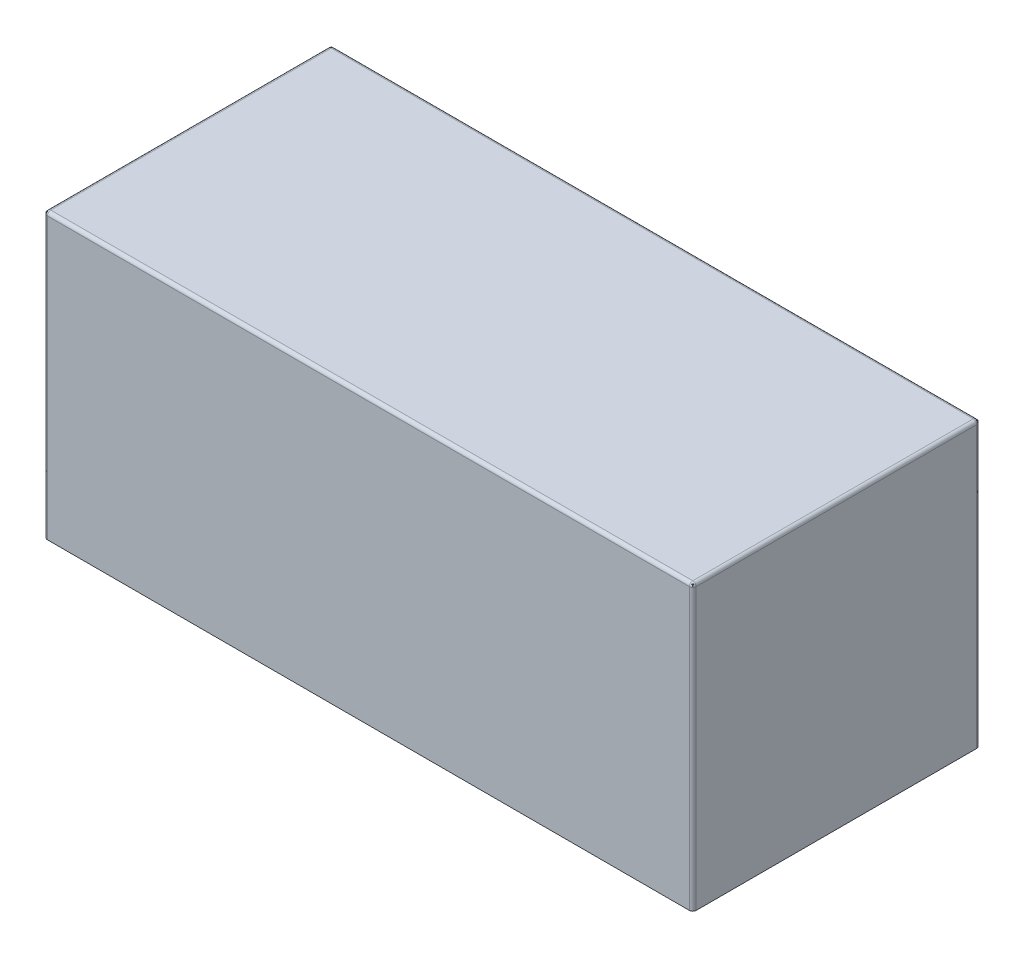
SolidWorks part; units mm, degrees
material "Alumina"
ref_plane "Front Plane" through (0, 0, 0) normal (0, 0, 1) x (1, 0, 0)
ref_plane "Top Plane" through (0, 0, 0) normal (0, 1, 0) x (1, 0, 0)
ref_plane "Right Plane" through (0, 0, 0) normal (1, 0, 0) x (0, 0, -1)
sketch "Sketch2" plane through (0, 0, 0) normal (0, 1, 0) x (1, 0, 0)
  line L1 (-480, 212.5) -> (480, 212.5)
  line L2 (-480, 212.5) -> (-480, -212.5)
  line L3 (-480, -212.5) -> (480, -212.5)
  line L4 (480, 212.5) -> (480, -212.5)
  line L5 (-480, 212.5) -> (480, -212.5) construction
  line L6 (-480, -212.5) -> (480, 212.5) construction
  line L7 (-478.4125, 210.9125) -> (478.4125, 210.9125)
  line L8 (-478.4125, 210.9125) -> (-478.4125, -210.9125)
  line L9 (-478.4125, -210.9125) -> (478.4125, -210.9125)
  line L10 (478.4125, 210.9125) -> (478.4125, -210.9125)
  line L11 (-478.4125, 210.9125) -> (478.4125, -210.9125) construction
  line L12 (-478.4125, -210.9125) -> (478.4125, 210.9125) construction
  point P0 (0, 0)
  point P6 (0, 0)
  dimension "D1" = 960
  dimension "D2" = 425
  dimension "D3" = 956.825
  dimension "D4" = 421.825
extrude "Boss-Extrude1" add sketch "Sketch2" along normal blind 420
sketch "Sketch3" plane through (0, 0, 0) normal (0, 1, 0) x (1, 0, 0)
  line L1 (-480, 212.5) -> (480, 212.5)
  line L2 (-480, 212.5) -> (-480, -212.5)
  line L3 (-480, -212.5) -> (480, -212.5)
  line L4 (480, 212.5) -> (480, -212.5)
  line L5 (-480, 212.5) -> (480, -212.5) construction
  line L6 (-480, -212.5) -> (480, 212.5) construction
  point P0 (0, 0)
  dimension "D1" = 960
  dimension "D2" = 425
extrude "Boss-Extrude2" add sketch "Sketch3" against normal blind 1.5875 from offset 420
fillet "Fillet2" radius 5 8 edges at (0, 420, 212.5) (-480, 420, 0) (0, 420, -212.5) (480, 420, 0) (480, 210, 212.5) (-480, 210, 212.5) (-480, 210, -212.5) (480, 210, -212.5)
sketch "Sketch4" plane through (-480, 0, 0) normal (-1, 0, 0) x (0, 0, 1)
  line L0 (-207.5, 0) -> (207.5, 0) construction
  line L1 (-40, 0) -> (40, 0)
  line L2 (-40, 0) -> (-40, 80)
  line L3 (-40, 80) -> (40, 80)
  line L4 (40, 0) -> (40, 80)
  line L5 (-40, 0) -> (40, 80) construction
  line L6 (-40, 80) -> (40, 0) construction
  point P4 (0, 40)
  dimension "D1" = 80
  dimension "D2" = 80
extrude "Cut-Extrude1" cut sketch "Sketch4" against normal up to next
sketch "Sketch5" plane through (0, 0, 212.5) normal (0, 0, 1) x (1, 0, 0)
  line L0 (102.4542, 1871.2645) -> (102.4542, 2121.2645) construction
  dimension "D1" = 250
sketch "Sketch6" plane through (0, 0, -212.5) normal (0, 0, -1) x (-1, 0, 0)
  line L0 (-163.7052, 31.2035) -> (-163.7052, 281.2035) construction
  dimension "D1" = 250
equation "\"sheetMetalThickness\"= 1in / 16"
equation "\"shellLength\"= 960mm"
equation "\"shellWidth\"= 425mm"
equation "\"shellHeight\"= 420mm"
equation "\"D1@Sketch2\"=\"shellLength\""
equation "\"D2@Sketch2\"=\"shellWidth\""
equation "\"D3@Sketch2\"=\"shellLength\"-\"sheetMetalThickness\"*2"
equation "\"D4@Sketch2\"=\"shellWidth\"-\"sheetMetalThickness\"*2"
equation "\"D1@Boss-Extrude1\"=\"shellHeight\""
equation "\"D1@Sketch3\"=\"shellLength\""
equation "\"D2@Sketch3\"=\"shellWidth\""
equation "\"D19@Boss-Extrude2\"=\"shellHeight\""
equation "\"D1@Boss-Extrude2\"=\"sheetMetalThickness\""
